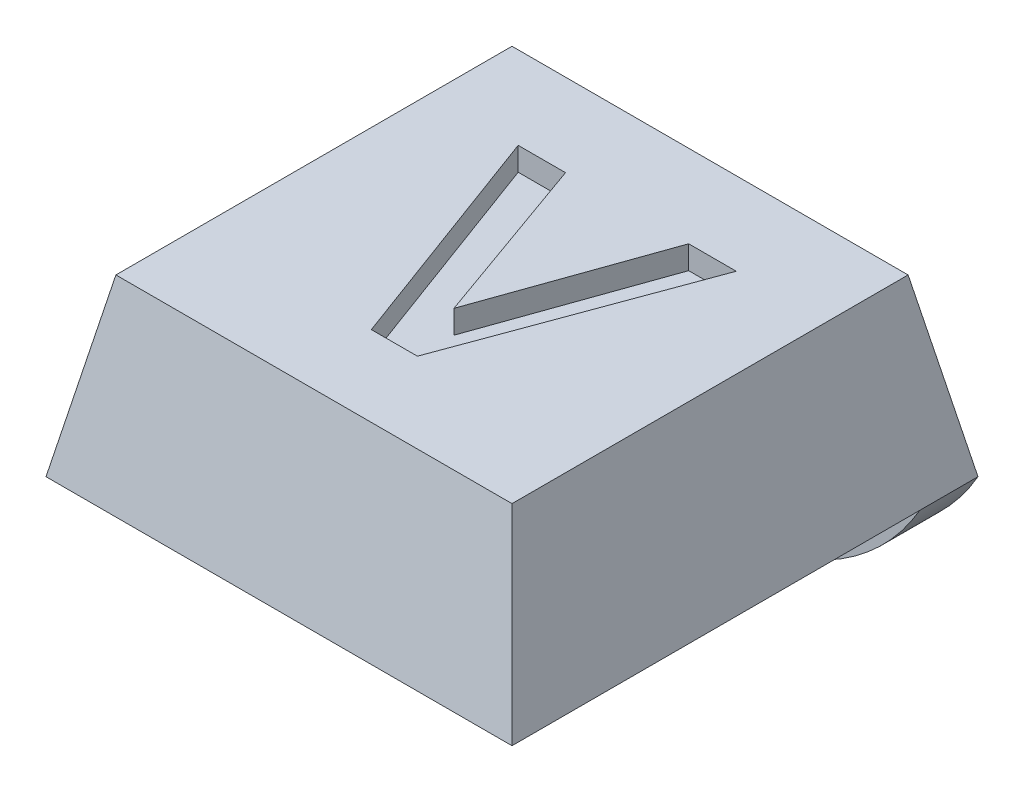
SolidWorks part; units mm, degrees
ref_plane "Front Plane" through (0, 0, 0) normal (0, 0, 1) x (1, 0, 0)
ref_plane "Top Plane" through (0, 0, 0) normal (0, 1, 0) x (1, 0, 0)
ref_plane "Right Plane" through (0, 0, 0) normal (1, 0, 0) x (0, 0, -1)
sketch "Sketch1" plane through (0, 0, 0) normal (0, 1, 0) x (1, 0, 0)
  line L1 (0, 0) -> (8, 0)
  line L2 (0, 0) -> (0, 8)
  line L3 (0, 8) -> (8, 8)
  line L4 (8, 0) -> (8, 8)
  dimension "D1" = 8
  dimension "D2" = 8
extrude "Boss-Extrude1" add sketch "Sketch1" along normal blind 3
sketch "Sketch2" plane through (0, 0, 0) normal (0, 0, 1) x (1, 0, 0)
  line L0 (0, 0) -> (0.6, 3)
  line L1 (0, 3) -> (8, 3) construction
  line L2 (0.6, 3) -> (0, 3)
  line L3 (0, 3) -> (0, 0)
  line L4 (8, 0) -> (7.4, 3)
  line L5 (7.4, 3) -> (8, 3)
  line L6 (8, 3) -> (8, 0)
  dimension "D1" = 0.6
  dimension "D2" = 0.6
extrude "Cut-Extrude1" cut sketch "Sketch2" against normal through all both and the other way through all
sketch "Sketch3" plane through (0, 0, 0) normal (1, 0, 0) x (0, 0, -1)
  line L0 (0, 0) -> (0.6, 3)
  line L1 (8, 3) -> (0, 3) construction
  line L2 (0.6, 3) -> (0, 3)
  line L3 (0, 3) -> (0, 0)
  line L4 (8, 3) -> (7.4, 3)
  line L5 (7.4, 3) -> (8, 0)
  line L6 (8, 3) -> (8, 0)
  dimension "D1" = 0.6
  dimension "D2" = 0.6
extrude "Cut-Extrude2" cut sketch "Sketch3" along normal blind 11
sketch "Sketch4" plane through (0, 0, 0) normal (0, -1, 0) x (1, 0, 0)
  line L0 (8, 0) -> (8, -8) construction
  line L3 (0, 0) -> (8, 0) construction
  circle A0 centre (4, -3.75) radius 1.8
  dimension "D1" = 3.6
  dimension "D2" = 4
  dimension "D3" = 3.75
extrude "Cut-Extrude3" cut sketch "Sketch4" against normal blind 0.8
sketch "Sketch5" plane through (0, 0, 0) normal (0, -1, 0) x (1, 0, 0)
  line L0 (8, 0) -> (8, -8) construction
  line L1 (0, -8) -> (8, -8)
  line L2 (0, -8) -> (0, -7)
  line L3 (0, -7) -> (8, -7)
  line L4 (8, -8) -> (8, -7)
  dimension "D1" = 1
extrude "Boss-Extrude2" add sketch "Sketch5" along normal blind 2
fillet "Fillet1" radius 4 2 edges at (8, -2, -7.5) (0, -2, -7.5)
sketch "Sketch6" plane through (0, 3, 0) normal (0, 1, 0) x (1, 0, 0)
  text T0 "V" font "Arial" height 4
extrude "Cut-Extrude4" cut sketch "Sketch6" against normal blind 0.4
